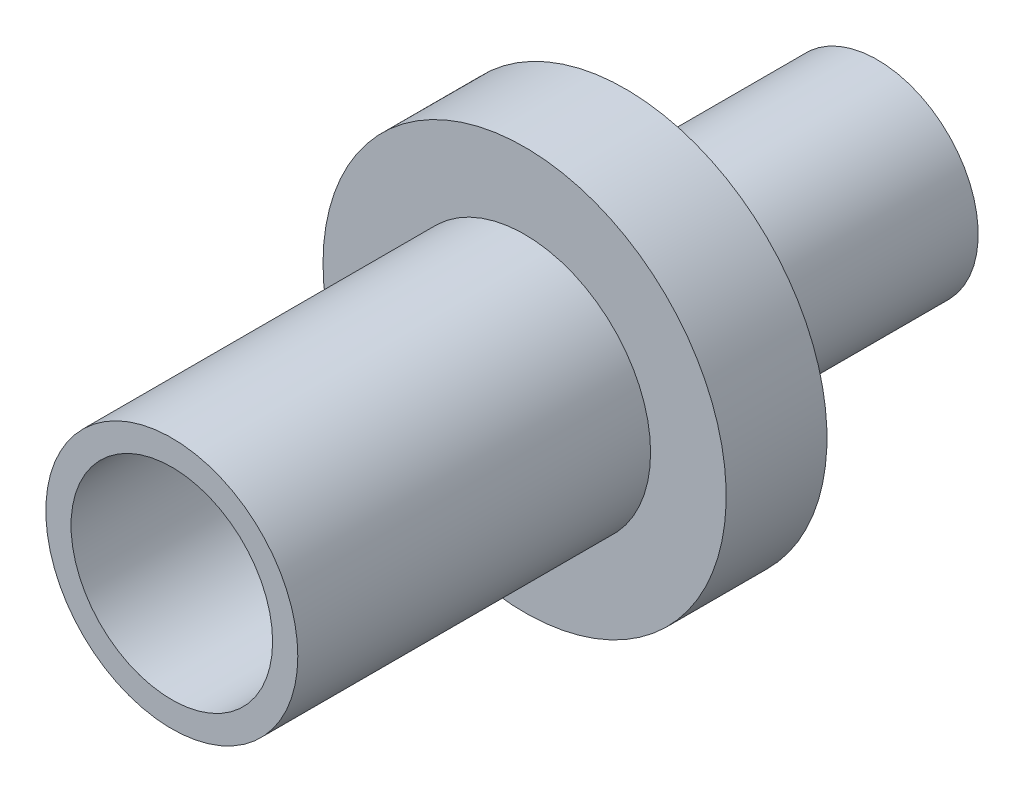
SolidWorks part; units mm, degrees
ref_plane "Front Plane" through (0, 0, 0) normal (0, 0, 1) x (1, 0, 0)
ref_plane "Top Plane" through (0, 0, 0) normal (0, 1, 0) x (1, 0, 0)
ref_plane "Right Plane" through (0, 0, 0) normal (1, 0, 0) x (0, 0, -1)
sketch "Sketch1" plane through (0, 0, 0) normal (0, 0, 1) x (1, 0, 0)
  circle A0 centre (-68.5859, -90) radius 2.5
extrude "Boss-Extrude1" add sketch "Sketch1" along normal blind 4 and the other way blind 3
sketch "Sketch2" plane through (0, 0, -3) normal (0, 0, -1) x (-1, 0, 0)
  circle A0 centre (68.5859, -90) radius 4
extrude "Boss-Extrude2" add sketch "Sketch2" along normal blind 2
sketch "Sketch3" plane through (0, 0, 4) normal (0, 0, 1) x (1, 0, 0)
  circle A2 centre (-68.5859, -90) radius 2
  circle A3 centre (-68.5859, -90) radius 2
  dimension "D1" = 0.5
extrude "Cut-Extrude1" cut sketch "Sketch3" against normal blind 5
sketch "Sketch4" plane through (0, 0, -5) normal (0, 0, -1) x (-1, 0, 0)
  circle A0 centre (68.5859, -90) radius 2
extrude "Boss-Extrude3" add sketch "Sketch4" along normal blind 5
